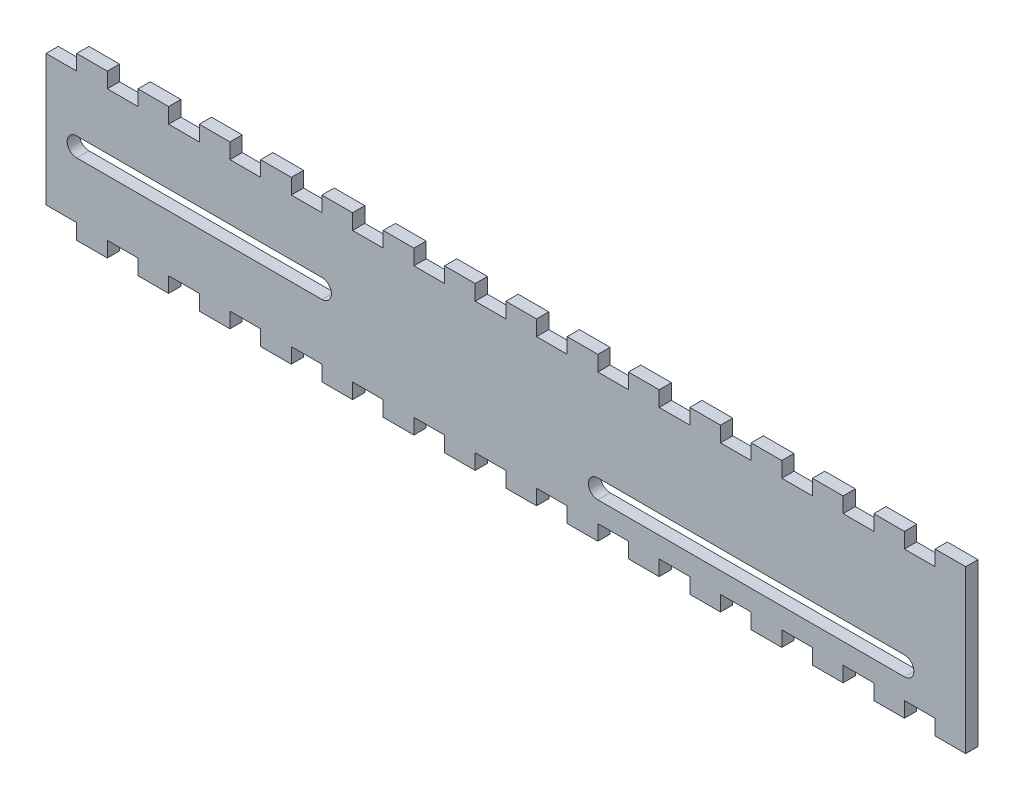
SolidWorks part; units mm, degrees
ref_plane "Front Plane" through (0, 0, 0) normal (0, 0, 1) x (1, 0, 0)
ref_plane "Top Plane" through (0, 0, 0) normal (0, 1, 0) x (1, 0, 0)
ref_plane "Right Plane" through (0, 0, 0) normal (1, 0, 0) x (0, 0, -1)
sketch "Sketch1" plane through (0, 0, 0) normal (0, 0, 1) x (1, 0, 0)
  line L0 (0, 10.7) -> (150, 10.7) construction
  line L1 (0, 0) -> (150, 0)
  line L2 (0, 0) -> (0, 21.4)
  line L3 (0, 21.4) -> (150, 21.4)
  line L4 (150, 0) -> (150, 21.4)
  dimension "D5" = 21.4
  dimension "D8" = 150
extrude "Boss-Extrude2" add sketch "Sketch1" along normal blind 2 contours L2 L0 L4 L3 | L0 L2 L1 L4 region at (75, 10.7, 0)
sketch "Sketch2" plane through (0, 21.4, 0) normal (0, 1, 0) x (1, 0, 0)
  line L1 (0, 0) -> (150, 0) construction
  line L2 (5, 0) -> (10, 0)
  line L3 (5, 0) -> (5, -2)
  line L4 (5, -2) -> (10, -2)
  line L5 (10, 0) -> (10, -2)
  line L6 (0, -2) -> (150, -2) construction
  line L7 (0, -2) -> (0, 0) construction
  dimension "D1" = 5
  dimension "D2" = 5
extrude "Boss-Extrude3" add sketch "Sketch2" along normal blind 2.5
pattern_linear "LPattern1" count 15 spacing 10 along (1, 0, 0) of "Boss-Extrude3"
sketch "Sketch3" plane through (0, 0, 0) normal (0, -1, 0) x (-1, 0, 0)
  line L1 (0, -2) -> (-150, -2) construction
  line L2 (-5, -2) -> (-10, -2)
  line L3 (-5, -2) -> (-5, 0)
  line L4 (-5, 0) -> (-10, 0)
  line L5 (-10, -2) -> (-10, 0)
  line L6 (0, 0) -> (-150, 0) construction
  line L7 (0, -2) -> (0, 0) construction
  point P9 (0, -1)
  dimension "D1" = 5
  dimension "D2" = 5
extrude "Boss-Extrude4" add sketch "Sketch3" along normal blind 2.5
pattern_linear "LPattern2" count 15 spacing 10 along (1, 0, 0) of "Boss-Extrude4"
sketch "Sketch4" plane through (0, 0, 0) normal (0, 0, -1) x (-1, 0, 0)
  line L0 (-140, 4.9) -> (-90, 4.9) construction
  line L1 (-140, 6.45) -> (-90, 6.45)
  line L2 (-140, 3.35) -> (-90, 3.35)
  line L3 (-150, -2.5) -> (-150, 23.9) construction
  line L4 (-150, -2.5) -> (-150, 23.9) construction
  line L5 (-120, 21.4) -> (-125, 21.4) construction
  line L6 (0, 10.7) -> (-150, 10.7) construction
  line L7 (0, 0) -> (0, 21.4) construction
  line L8 (-45, 10.7) -> (-5, 10.7) construction
  line L9 (-45, 12.25) -> (-5, 12.25)
  line L10 (-45, 9.15) -> (-5, 9.15)
  arc A0 (-140, 6.45) -> (-140, 3.35) centre (-140, 4.9) ccw
  arc A1 (-90, 3.35) -> (-90, 6.45) centre (-90, 4.9) ccw
  arc A2 (-45, 12.25) -> (-45, 9.15) centre (-45, 10.7) ccw
  arc A3 (-5, 9.15) -> (-5, 12.25) centre (-5, 10.7) ccw
  point P2 (-115, 4.9)
  point P19 (-25, 10.7)
  dimension "D2" = 1.55
  dimension "D7" = 1.55
  dimension "D1" = 10
  dimension "D3" = 50
  dimension "D4" = 16.5
  dimension "D5" = 40
  dimension "D6" = 5
extrude "Cut-Extrude1" cut sketch "Sketch4" against normal blind 10
